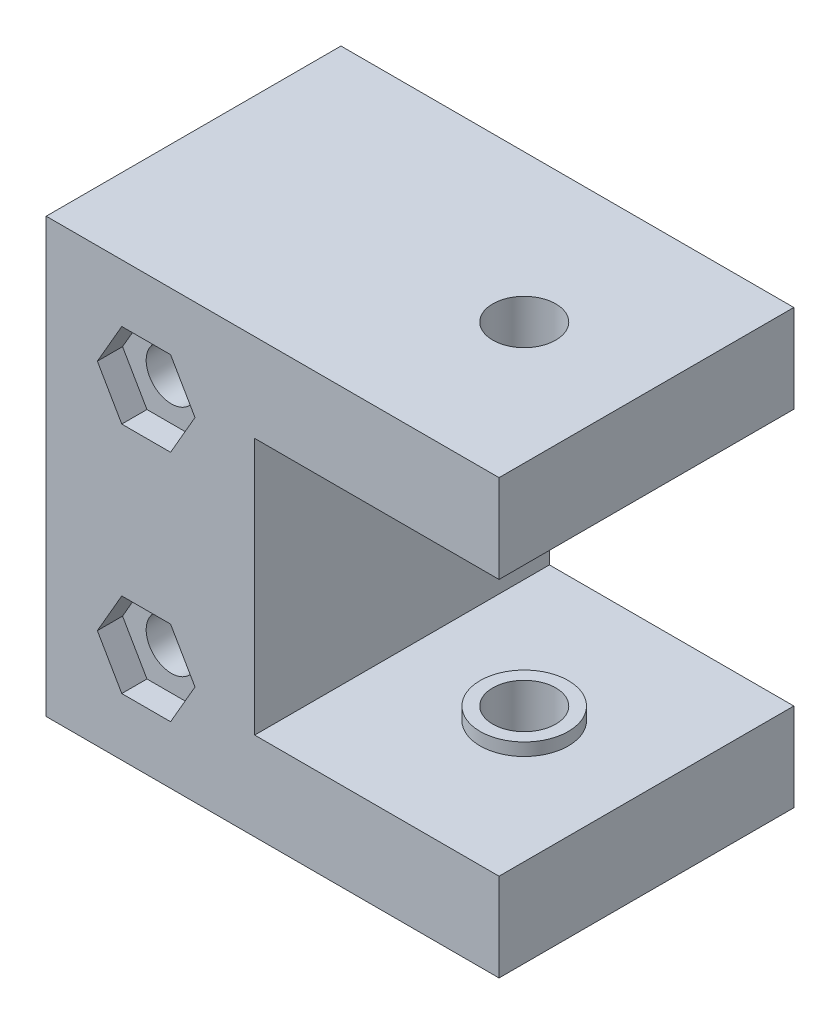
SolidWorks part; units mm, degrees
ref_plane "Front Plane" through (0, 0, 0) normal (0, 0, 1) x (1, 0, 0)
ref_plane "Top Plane" through (0, 0, 0) normal (0, 1, 0) x (1, 0, 0)
ref_plane "Right Plane" through (0, 0, 0) normal (1, 0, 0) x (0, 0, -1)
sketch "MainBlock" plane through (0, 0, 0) normal (0, 0, 1) x (1, 0, 0)
  line L0 (0, 0) -> (35.95, 0)
  line L1 (35.95, 0) -> (35.95, 7)
  line L2 (35.95, 7) -> (16.55, 7)
  line L3 (16.55, 7) -> (16.55, 27.4)
  line L4 (16.55, 27.4) -> (35.95, 27.4)
  line L5 (35.95, 27.4) -> (35.95, 34.4)
  line L6 (35.95, 34.4) -> (0, 34.4)
  line L7 (0, 34.4) -> (0, 0)
  circle A0 centre (7.9375, 26.4625) radius 2
  circle A1 centre (7.9375, 7.9375) radius 2
  dimension "D4" = 4
  dimension "D1" = 35.95
  dimension "D2" = 34.4
  dimension "D3" = 20.4
  dimension "D5" = 19.4
  dimension "D6" = 7.9375
  dimension "D7" = 7.9375
  dimension "D8" = 7.9375
extrude "MainBlockBoss-Extrude1" add sketch "MainBlock" along normal blind 23.4
sketch "TopHoleCut-Sketch2" plane through (0, 34.4, 0) normal (0, 1, 0) x (1, 0, 0)
  line L0 (35.95, 0) -> (0, 0) construction
  line L1 (0, -23.4) -> (0, 0) construction
  circle A0 centre (26.25, -11.7) radius 2.5
  dimension "D3" = 5
  dimension "D1" = 11.7
  dimension "D2" = 26.25
extrude "TopHoleCut-Extrude1" cut sketch "TopHoleCut-Sketch2" against normal blind 30
sketch "MountHoleBoreSketch3" plane through (0, 0, 23.4) normal (0, 0, 1) x (1, 0, 0)
  line L1 (11.8125, 26.4625) -> (9.875, 29.8183)
  line L2 (9.875, 29.8183) -> (6, 29.8183)
  line L3 (6, 29.8183) -> (4.0625, 26.4625)
  line L4 (4.0625, 26.4625) -> (6, 23.1067)
  line L5 (6, 23.1067) -> (9.875, 23.1067)
  line L6 (9.875, 23.1067) -> (11.8125, 26.4625)
  line L7 (11.8125, 7.9375) -> (9.875, 11.2933)
  line L8 (9.875, 11.2933) -> (6, 11.2933)
  line L9 (6, 11.2933) -> (4.0625, 7.9375)
  line L10 (4.0625, 7.9375) -> (6, 4.5817)
  line L11 (6, 4.5817) -> (9.875, 4.5817)
  line L12 (9.875, 4.5817) -> (11.8125, 7.9375)
  circle A0 centre (7.9375, 26.4625) radius 3.3558 construction
  circle A1 centre (7.9375, 7.9375) radius 3.3558 construction
  point P10 (7.9375, 29.8183)
  dimension "D1" = 7.75
extrude "MountHoleBoreCut-Extrude2" cut sketch "MountHoleBoreSketch3" against normal blind 2
sketch "TopSpacerSketch4" plane through (0, 27.4, 0) normal (0, -1, 0) x (1, 0, 0)
  circle A0 centre (26.25, 11.7) radius 3.5
  circle A1 centre (26.25, 11.7) radius 2.5
  circle A2 centre (26.25, 11.7) radius 2.5 construction
  dimension "D1" = 7
extrude "TopSpacerBoss-Extrude2" add sketch "TopSpacerSketch4" along normal blind 1
sketch "LowerSpacerSketch5" plane through (0, 7, 0) normal (0, 1, 0) x (1, 0, 0)
  circle A0 centre (26.25, -11.7) radius 2.5
  circle A1 centre (26.25, -11.7) radius 2.5 construction
  circle A2 centre (26.25, -11.7) radius 3.5
  circle A3 centre (26.25, -11.7) radius 3.5 construction
extrude "LowerSpacerBoss-Extrude3" add sketch "LowerSpacerSketch5" along normal blind 1
sketch "PushPinHoleSketch1" plane through (0, 0, 0) normal (0, -1, 0) x (1, 0, 0)
  circle A0 centre (26.25, 11.7) radius 1
  circle A1 centre (26.25, 11.7) radius 2.5 construction
  dimension "D1" = 2
extrude "PushPinHoleCut-Extrude1" cut sketch "PushPinHoleSketch1" against normal through all
equation "\"BeltTensionerWidth\"= \"MidRailToAlignWithGantryBlock\" + \"BeltTensionerInnerWidth\" / 2"
equation "\"BeltTensionerHeight\"= \"BeltTensionerInnerHeight\" + \"BeltTensionerUpperLowerWallThickness\" * 2"
equation "\"BeltTensionerDepth\"= \"BeltTensionerBackWallThickness\" + \"BeltTensionerInnerDepth\"'Equals 23.4"
equation "\"BeltTensionerUpperLowerWallThickness\"= 7mm"
equation "\"BeltTensionerInnerWidth\"= \"20TGT2PulleyDiameter\" + \"BeltTensionerSpaceBetweenPulleyAndWall\""
equation "\"BeltTensionerInnerHeight\"= \"20TGT2PulleyWidth\" * 2 + \"1mmSpacer\" * 3"
equation "\"BeltTensionerBackWallThickness\"= 4mm"
equation "\"BeltTensionerInnerDepth\"= \"20TGT2PulleyDiameter\" + \"BeltTensionerSpaceBetweenPulleyAndWall\""
equation "\"RailThickness\"= .125in'Spec"
equation "\"HoleOffsetFromEdge\"= \"RailThickness\" * 2.5"
equation "\"LinearGBWithRailDepth\"= 12.75mm'Spec"
equation "\"GABDistanceFromBackToFirstPulley\"= 13.5mm"
equation "\"MidRailToAlignWithGantryBlock\"= \"LinearGBWithRailDepth\" + \"GABDistanceFromBackToFirstPulley\"'All outside cogs must align"
equation "\"20TGT2PulleyDiameter\"= 17.9mm'Spec"
equation "\"BeltTensionerSpaceBetweenPulleyAndWall\"= 1.5mm"
equation "\"BeltTensionerMountingHoleDiameter\"= 4.0mm"
equation "\"BeltTensionerMountingHoleOffsetFromEdge\"= \"HoleOffsetFromEdge\""
equation "\"20TGT2PulleyWidth\"= 8.7mm'The STL of the Pulley in the diagram is a bit larger"
equation "\"1mmSpacer\"= 1mm"
equation "\"SteelShaft5mmHoleDiameter\"= 5mm"
equation "\"BeltTensionerMountingHoleOuterBoreDepth\"= 2mm"
equation "\"BeltTensionerMountingHoleOuterBoreDiameter\"= 7.75mm"
equation "\"7mmx1mmSpacerDiameter\"= 7mm"
equation "\"7mmx1mmSpacerHeight\"= 1mm"
equation "\"D1@MainBlock\" = \"BeltTensionerWidth\""
equation "\"D2@MainBlock\" = \"BeltTensionerHeight\""
equation "\"D3@MainBlock\" = \"BeltTensionerInnerHeight\""
equation "\"D4@MainBlock\" = \"BeltTensionerMountingHoleDiameter\""
equation "\"D5@MainBlock\" = \"BeltTensionerInnerWidth\""
equation "\"D6@MainBlock\"=\"BeltTensionerMountingHoleOffsetFromEdge\""
equation "\"D7@MainBlock\" = \"HoleOffsetFromEdge\""
equation "\"D8@MainBlock\" = \"HoleOffsetFromEdge\""
equation "\"D1@MainBlockBoss-Extrude1\" = \"BeltTensionerDepth\""
equation "\"D1@TopHoleCut-Sketch2\" = \"BeltTensionerDepth\" / 2"
equation "\"D2@TopHoleCut-Sketch2\" = \"MidRailToAlignWithGantryBlock\""
equation "\"D3@TopHoleCut-Sketch2\" = \"SteelShaft5mmHoleDiameter\""
equation "\"D1@MountHoleBoreSketch3\" = \"BeltTensionerMountingHoleOuterBoreDiameter\""
equation "\"D1@MountHoleBoreCut-Extrude2\"=\"BeltTensionerMountingHoleOuterBoreDepth\""
equation "\"D1@TopSpacerSketch4\" = \"7mmx1mmSpacerDiameter\""
equation "\"D1@TopSpacerBoss-Extrude2\" = \"7mmx1mmSpacerHeight\""
equation "\"D1@LowerSpacerBoss-Extrude3\" = \"7mmx1mmSpacerHeight\""
equation "\"StealPinPushHoleDiameter\"= 2mm"
equation "\"D1@PushPinHoleSketch1\" = \"StealPinPushHoleDiameter\""
